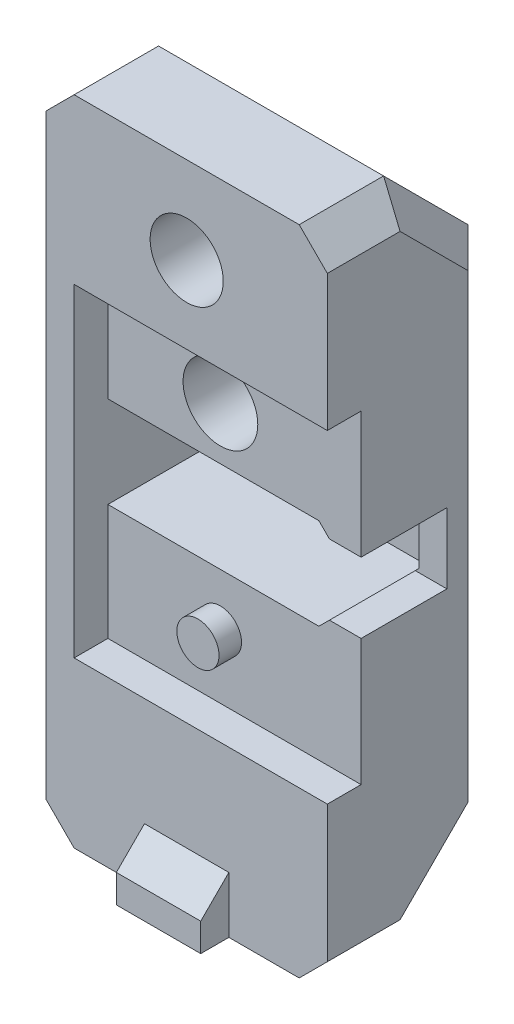
SolidWorks part; units mm, degrees
ref_plane "Front Plane" through (0, 0, 0) normal (0, 0, 1) x (1, 0, 0)
ref_plane "Top Plane" through (0, 0, 0) normal (0, 1, 0) x (1, 0, 0)
ref_plane "Right Plane" through (0, 0, 0) normal (1, 0, 0) x (0, 0, -1)
sketch "Sketch1" plane through (0, 0, 0) normal (0, 0, 1) x (1, 0, 0)
  line L0 (-9.1971, 11.5) -> (-9.1971, -11.5)
  line L3 (-11.1971, 23.1752) -> (8.8029, 23.1752)
  line L5 (-11.1971, -23.2072) -> (8.8029, -23.2072)
  line L6 (-9.1971, -11.5) -> (8.8029, -11.5)
  line L7 (-9.1971, 11.5) -> (8.8029, 11.5)
  line L8 (-11.1971, 23.1752) -> (-11.1971, -23.2072)
  line L9 (8.8029, 23.1752) -> (8.8029, -23.2072)
  circle A0 centre (-1.1971, 16.984) radius 2.6
  circle A4 centre (-1.1971, 7) radius 1.75
  circle A5 centre (-1.1971, 7) radius 3.25
  circle A7 centre (-1.1971, 0) radius 2.75
  dimension "D1" = 5.5
  dimension "D2" = 3.5
  dimension "D3" = 7
extrude "Boss-Extrude2" add sketch "Sketch1" along normal blind 2
sketch "Sketch2" plane through (0, 0, 2) normal (0, 0, 1) x (1, 0, 0)
  line L0 (-11.1971, -23.2072) -> (8.8029, -23.2072) construction
  line L1 (8.8029, 23.1752) -> (8.8029, -23.2072) construction
  line L2 (-11.1971, 23.1752) -> (8.8029, 23.1752) construction
  line L3 (-11.1971, 23.1752) -> (-11.1971, -23.2072) construction
  line L4 (-9.1971, -11.5) -> (8.8029, -11.5) construction
  line L5 (-9.1971, 11.5) -> (-9.1971, -11.5) construction
  line L6 (-9.1971, 11.5) -> (8.8029, 11.5) construction
  line L7 (-11.1971, -23.2072) -> (8.8029, -23.2072)
  line L8 (8.8029, 23.1752) -> (8.8029, -23.2072)
  line L9 (-11.1971, 23.1752) -> (8.8029, 23.1752)
  line L10 (-11.1971, 23.1752) -> (-11.1971, -23.2072)
  line L11 (-9.1971, -11.5) -> (8.8029, -11.5)
  line L12 (-9.1971, 11.5) -> (-9.1971, -11.5)
  line L13 (-9.1971, 11.5) -> (8.8029, 11.5)
  circle A1 centre (-1.1971, 16.984) radius 2.6 construction
  circle A3 centre (-1.1971, 7) radius 3.25 construction
  circle A4 centre (-1.1971, 7) radius 1.75 construction
  circle A8 centre (-1.1971, 16.984) radius 2.6
  circle A10 centre (-1.1971, 7) radius 3.25
  circle A11 centre (-1.1971, 7) radius 1.75
extrude "Boss-Extrude3" add sketch "Sketch2" along normal blind 10
sketch "Sketch3" plane through (0, 0, 2) normal (0, 0, 1) x (1, 0, 0)
  line L0 (-9.1971, 0) -> (8.8029, 0) construction
  line L3 (-9.1971, 11.5) -> (-9.1971, -11.5) construction
  line L5 (-9.1971, 11.5) -> (-9.1971, -11.5) construction
  line L6 (-9.1971, 11.5) -> (8.8029, 11.5) construction
  line L7 (8.8029, 3.25) -> (8.8029, 0)
  line L8 (8.8029, -3.25) -> (8.8029, -11.5)
  line L9 (-9.1971, -3.25) -> (8.8029, -3.25)
  line L10 (-9.1971, -11.5) -> (8.8029, -11.5)
  line L11 (-9.1971, -11.5) -> (-9.1971, -3.25)
  line L12 (-9.1971, 11.5) -> (-9.1971, 3.25)
  line L13 (-9.1971, 11.5) -> (8.8029, 11.5)
  line L14 (-9.1971, 3.25) -> (8.8029, 3.25)
  line L15 (8.8029, 3.25) -> (8.8029, 11.5)
  circle A1 centre (-1.1971, 16.984) radius 2.6 construction
  circle A2 centre (-1.1971, -7) radius 1.75
  circle A4 centre (-1.1971, 7) radius 1.75 construction
  circle A8 centre (-1.1971, 16.984) radius 2.6
  circle A11 centre (-1.1971, 7) radius 1.75
  dimension "D1" = 6.5
sketch "Sketch4" plane through (0, 0, 0) normal (0, 0, -1) x (-1, 0, 0)
  circle A0 centre (1.1971, 7) radius 1.75
  dimension "D1" = 3.5
extrude "Boss-Extrude5" add sketch "Sketch4" against normal blind 2
sketch "Sketch5" plane through (0, 0, 0) normal (0, 0, -1) x (-1, 0, 0)
  circle A0 centre (1.1971, 16.984) radius 4.5
  dimension "D1" = 9
extrude "Cut-Extrude1" cut sketch "Sketch5" against normal blind 5
extrude "Boss-Extrude9" add sketch "Sketch3" along normal blind 7.6
sketch "Sketch8" plane through (0, 0, 9.6) normal (0, 0, 1) x (1, 0, 0)
  circle A0 centre (-1.1971, 7) radius 2.55
  dimension "D1" = 5.1
extrude "Cut-Extrude3" cut sketch "Sketch8" against normal blind 3.8
chamfer "Chamfer5" distance 0.105 distance2 3.8 1 edges at (1.3529, 7, 9.6) first distance on face at (1.3529, 7, 9.6)
chamfer "Chamfer6" distance 6 angle 45 2 edges at (-1.1971, 23.1752, 0) (-1.1971, -23.2072, 0)
chamfer "Chamfer7" distance 2 angle 45 10 edges at (-11.1971, 23.1752, 9) (-11.1971, -23.2072, 9) (-11.1971, -20.2072, 3) (-11.1971, -0.016, 0) (-11.1971, 20.1752, 3) (8.8029, 23.1752, 9) (8.8029, -23.2072, 9) (8.8029, -20.2072, 3) (8.8029, 20.1752, 3) (8.8029, -0.016, 0)
sketch "Sketch9" plane through (0, 0, 2) normal (0, 0, 1) x (1, 0, 0)
  line L0 (8.8029, 3.25) -> (8.8029, -3.25)
  line L1 (8.8029, -3.25) -> (6.8029, -3.25)
  line L2 (-9.1971, -3.25) -> (8.8029, -3.25) construction
  line L3 (6.8029, -3.25) -> (6.8029, 3.25)
  line L4 (-9.1971, 3.25) -> (8.8029, 3.25) construction
  line L5 (6.8029, 3.25) -> (8.8029, 3.25)
  dimension "D1" = 2
extrude "Boss-Extrude10" add sketch "Sketch9" along normal blind 1.5
sketch "Sketch10" plane through (0, 0, 3.5) normal (0, 0, 1) x (1, 0, 0)
  line L0 (8.8029, 3.25) -> (6.8029, 3.25)
  line L1 (6.8029, 3.25) -> (6.8029, 2.5)
  line L2 (6.8029, 3.25) -> (6.8029, -3.25) construction
  line L3 (6.8029, 2.5) -> (8.8029, 2.5)
  line L4 (8.8029, -3.25) -> (8.8029, 3.25) construction
  line L5 (8.8029, 2.5) -> (8.8029, 3.25)
  line L10 (-9.1971, 0) -> (8.8029, 0) construction
  line L11 (-9.1971, 11.5) -> (-9.1971, -11.5) construction
  line L12 (8.8029, -2.5) -> (8.8029, -3.25)
  line L13 (6.8029, -2.5) -> (8.8029, -2.5)
  line L14 (6.8029, -3.25) -> (6.8029, -2.5)
  line L15 (8.8029, -3.25) -> (6.8029, -3.25)
  dimension "D1" = 0.75
extrude "Boss-Extrude11" add sketch "Sketch10" along normal up to surface (6.1 mm away) up to face at (1.4579, 7, 9.6)
chamfer "Chamfer8" distance 1 angle 45 3 edges at (6.8029, -3.25, 5.8) (6.8029, 0, 2) (6.8029, 3.25, 5.8)
sketch "Sketch13" plane through (0, 0, 2) normal (0, 0, 1) x (1, 0, 0)
  circle A0 centre (-1.1971, -7) radius 1.876
extrude "Boss-Extrude14" add sketch "Sketch13" along normal up to surface (7.6 mm away) up to face at (1.9279, -5.75, 9.6)
sketch "Sketch12" plane through (0, 0, 9.6) normal (0, 0, 1) x (1, 0, 0)
  circle A1 centre (-1.1971, -7) radius 1.5
  dimension "D1" = 3
  dimension "D2" = 7
extrude "Boss-Extrude15" add sketch "Sketch12" along normal blind 1.6
sketch "Sketch14" plane through (0, 0, 12) normal (0, 0, 1) x (1, 0, 0)
  line L0 (-1.1971, 23.1752) -> (-1.1971, -23.2072) construction
  line L1 (6.8029, 23.1752) -> (-9.1971, 23.1752) construction
  line L2 (-9.1971, -23.2072) -> (6.8029, -23.2072) construction
  line L3 (1.8029, -19.2072) -> (1.8029, -23.2072)
  line L16 (-4.1971, -19.2072) -> (-4.1971, -23.2072)
  line L17 (-4.1971, -23.2072) -> (1.8029, -23.2072)
  line L18 (-4.1971, -19.2072) -> (1.8029, -19.2072)
  line L20 (-4.1971, 23.1752) -> (-4.1971, -23.2072) construction
  line L21 (1.8029, 23.1752) -> (1.8029, -23.2072) construction
  dimension "D1" = 3
  dimension "D2" = 3
  dimension "D3" = 4
extrude "Boss-Extrude16" add sketch "Sketch14" along normal blind 2
chamfer "Chamfer9" distance 2 angle 45 1 edges at (-1.1971, -19.2072, 14)
